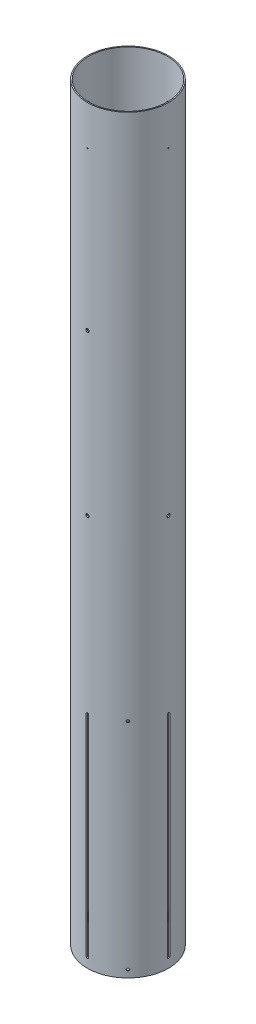
SolidWorks part; units mm, degrees
material "C-Glass Fiber"
ref_plane "Front Plane" through (0, 0, 0) normal (0, 0, 1) x (1, 0, 0)
ref_plane "Top Plane" through (0, 0, 0) normal (0, 1, 0) x (1, 0, 0)
ref_plane "Right Plane" through (0, 0, 0) normal (1, 0, 0) x (0, 0, -1)
sketch "Sustainer Tube Profile" plane through (0, 0, 0) normal (0, 1, 0) x (1, 0, 0)
  circle A0 centre (0, 0) radius 76.2
  circle A1 centre (0, 0) radius 78.359
  dimension "D2" = 156.718
extrude "Sustainer Tube Body" add sketch "Sustainer Tube Profile" along normal blind 1447.8
ref_plane "Plane1" through (0, 0, 78.359) normal (0, 0, 1) x (1, 0, 0)
sketch "Fin Slot Profile" plane through (0, 0, 78.359) normal (0, 0, 1) x (1, 0, 0)
  line L0 (0, 0) -> (0, 1447.8) construction
  line L5 (76.2, 1447.8) -> (-76.2, 1447.8) construction
  line L6 (-78.359, 0) -> (78.359, 0) construction
  line L7 (2.3813, 19.05) -> (-2.3813, 19.05)
  line L8 (0, 19.05) -> (0, 425.45)
  line L9 (2.3813, 425.45) -> (-2.3813, 425.45)
  line L10 (-2.3813, 19.05) -> (-2.3813, 425.45)
  line L11 (2.3813, 19.05) -> (2.3813, 425.45)
  arc A0 (-2.3813, 19.05) -> (2.3812, 19.05) centre (0, 19.05) ccw
  arc A1 (2.3813, 425.45) -> (-2.3812, 425.45) centre (0, 425.45) ccw
  dimension "D1" = 406.4
  dimension "D2" = 19.05
  dimension "D3" = 2.3813
extrude "Fin Slot Cut" cut sketch "Fin Slot Profile" against normal up to surface (2.1962 mm away) contours L7 L11 L9 L8 | L10 L7 L8 L9 | L0 L9 A1 | L9 L0 A1 | A0 L0 L7 | L0 A0 L7 region at (-1.1906, 222.25, 78.359) region at (1.0106, 18.0394, 78.359) region at (1.1906, 222.25, 78.359) region at (-1.0106, 18.0394, 78.359) region at (-1.0106, 426.4606, 78.359) region at (1.0106, 426.4606, 78.359) up to face at (0, 1447.8, 76.2)
pattern_circular "Fin Slot Pattern" count 4 over 360 about axis through (0, 1447.8, 0) along (0, 1, 0) of "Fin Slot Cut"
sketch "Sketch1" plane through (0, 0, 0) normal (0, 0, 1) x (1, 0, 0)
  line L0 (76.2, 1447.8) -> (-76.2, 1447.8) construction
  circle A0 centre (0, 1371.6) radius 1.143
  dimension "D1" = 2.286
  dimension "D2" = 76.2
extrude "Cut-Extrude1" cut sketch "Sketch1" against normal through all both and the other way through all
pattern_circular "CirPattern1" count 4 over 360 about axis through (0, 1447.8, 0) along (0, 1, 0) of "Cut-Extrude1"
sketch "Sketch2" plane through (0, 0, 0) normal (0, 0, 1) x (1, 0, 0)
  line L0 (76.2, 1447.8) -> (-76.2, 1447.8) construction
  circle A0 centre (0, 1066.8) radius 3.175
  dimension "D1" = 6.35
  dimension "D2" = 381
extrude "Cut-Extrude2" cut sketch "Sketch2" against normal through all both and the other way through all
sketch "Sketch3" plane through (0, 0, 0) normal (0, 0, 1) x (1, 0, 0)
  line L0 (78.359, 1447.8) -> (-78.359, 1447.8) construction
  circle A0 centre (0, 756.9962) radius 3.175
  dimension "D2" = 6.35
  dimension "D1" = 690.8038
extrude "Cut-Extrude3" cut sketch "Sketch3" against normal through all both and the other way through all
pattern_circular "CirPattern2" count 4 over 360 about axis through (0, 1447.8, 0) along (0, 1, 0) of "Cut-Extrude3"
ref_plane "Plane2" through (55.4082, 0, 55.4082) normal (0.7071, 0, 0.7071) x (0, -1, 0)
sketch "Sketch4" plane through (55.4082, 0, 55.4082) normal (0.7071, 0, 0.7071) x (0, -1, 0)
  circle A0 centre (-14.0462, 0) radius 2.5019
  circle A1 centre (-429.4429, 0) radius 2.5019
  dimension "D2" = 14.0462
  dimension "D3" = 429.4429
extrude "Cut-Extrude4" cut sketch "Sketch4" against normal up to surface and the other way through all up to face at (-76.1373, 756.269, 3.0906)
ref_plane "Plane3" through (0, 0, 0) normal (0.7071, 0, 0.7071) x (0, -1, 0)
sketch "Sketch7" plane through (0, 0, 0) normal (0, -1, 0) x (1, 0, 0)
  line L0 (0, -76.2) -> (0, 76.2) construction
  line L1 (-76.2, 0) -> (76.2, 0) construction
  point P5 (0, 0)
  point P9 (0, 0)
sketch "Sketch8" plane through (0, 0, 0) normal (0, -1, 0) x (1, 0, 0)
  line L0 (0, -76.2) -> (0, 76.2) construction
  line L1 (0, -76.2) -> (0, 76.2) construction
equation "\"Length\"= 57"
equation "\"Outer Diameter\"= 6.17"
equation "\"Inner Diameter\"= 6"
equation "\"Wall Thickness\"= 0.085"
equation "\"D1@Sustainer Tube Profile\" = \"Inner Diameter\""
equation "\"D2@Sustainer Tube Profile\" = \"Outer Diameter\""
equation "\"D1@Sustainer Tube Body\" = \"Length\""
equation "\"Root Chord\"= 16"
equation "\"Fin Offset\"= 3 / 4"
equation "\"D1@Fin Slot Profile\"=\"Root Chord\" "
equation "\"D2@Fin Slot Profile\" = \"Fin Offset\""
equation "\"Fin Thickness\"= ( 3 / 16 ) / 2"
equation "\"D3@Fin Slot Profile\"=\"Fin Thickness\""
equation "\"Shear Pin Dia\"= 3 / 32"
equation "\"Shear Pin Offset\"= 3"
equation "\"Bulkhead Screw Dia\"= 1 / 4"
equation "\"Bulkhead Screw Offset\"= 24.197 + 3"
equation "\"Rail Button Dia\"= 0.197"
equation "\"Rail Button Aft Offset\"= 0.553"
equation "\"Rail Button Forward Offset\"= 16.9072"
equation "\"Vent Hole Dia\"= 1 / 4"
equation "\"Vent Hole Offset\"= 15"
equation "\"D1@Sketch2\"=\"Vent Hole Dia\""
equation "\"D2@Sketch2\"=\"Vent Hole Offset\""
equation "\"D1@Sketch3\"=\"Bulkhead Screw Offset\""
equation "\"D2@Sketch3\"=\"Bulkhead Screw Dia\""
equation "\"D1@Sketch4\"=\"Rail Button Dia\""
equation "\"D2@Sketch4\"=\"Rail Button Aft Offset\""
equation "\"D3@Sketch4\"=\"Rail Button Forward Offset\""
